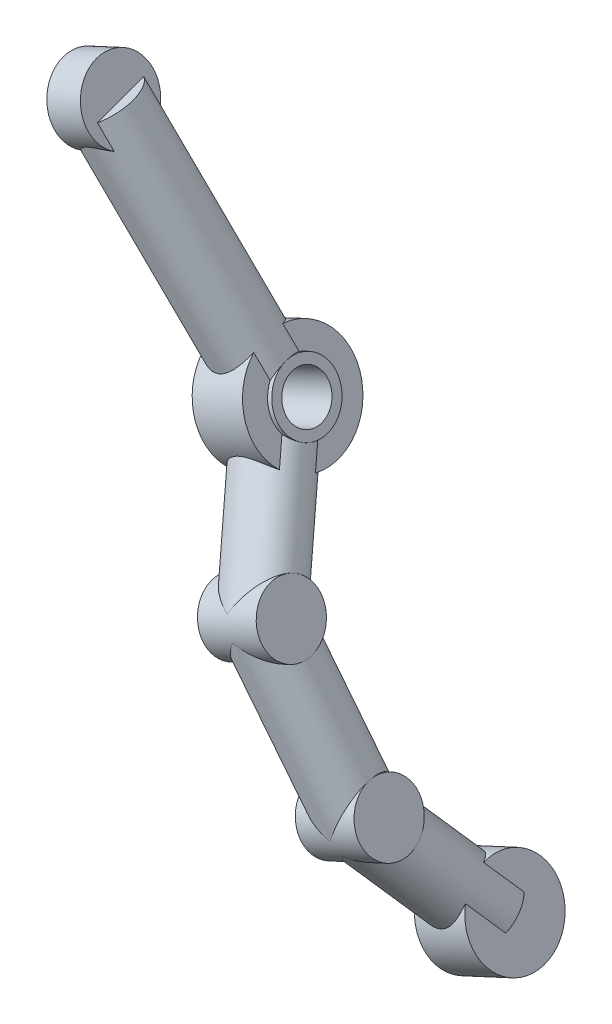
SolidWorks part; units mm, degrees
ref_plane "Alzado" through (0, 0, 0) normal (0, 0, 1) x (1, 0, 0)
ref_plane "Planta" through (0, 0, 0) normal (0, 1, 0) x (1, 0, 0)
ref_plane "Vista lateral" through (0, 0, 0) normal (1, 0, 0) x (0, 0, -1)
sketch3d "Sk_Brazo_1"
  line L0 (424.6109, 411.5791, 33) -> (436.398, 386.181, 26)
  dimension "D1" = 28.8617
sweep "Brazo_1" add path "Sk_Brazo_1" circular profile diameter 7 parameters "D3"=7
sketch3d "Sk_Brazo_2"
  line L0 (436.398, 386.181, 26) -> (442.7125, 372.5749, 34)
  dimension "D1" = 17
sweep "Brazo_2" add path "Sk_Brazo_2" circular profile diameter 7 parameters "D3"=7
sketch3d "Sk_Brazo_3"
  line L0 (442.7125, 372.5749, 34) -> (450.2899, 356.2475, 31)
  dimension "D1" = 18.2483
sweep "Brazo_3" add path "Sk_Brazo_3" circular profile diameter 7 parameters "D3"=7
sketch3d "Sk_Brazo_4"
  line L0 (450.2899, 356.2475, 31) -> (455.3416, 345.3626, 22)
  dimension "D1" = 15
sweep "Brazo_4" add path "Sk_Brazo_4" circular profile diameter 7 parameters "D3"=7
sketch3d "Sk_Brazo_codo_1"
  line L0 (433.2232, 384.7076, 26) -> (439.5728, 387.6544, 26)
  dimension "D1" = 7
sweep "Brazo_codo_1" add path "Sk_Brazo_codo_1" circular profile diameter 7 parameters "D3"=7
sketch3d "Sk_Brazo_codo_2"
  line L0 (439.5378, 371.1015, 34) -> (445.8873, 374.0483, 34)
  dimension "D1" = 7
sweep "Brazo_codo_2" add path "Sk_Brazo_codo_2" circular profile diameter 7 parameters "D3"=7
sketch3d "Sk_Brazo_codo_3"
  line L0 (447.1152, 354.7741, 31) -> (453.4647, 357.7209, 31)
  dimension "D1" = 7
sweep "Brazo_codo_3" add path "Sk_Brazo_codo_3" circular profile diameter 7 parameters "D3"=7
sketch3d "Sk_Ojo_pivote"
  line L0 (433.6768, 384.9181, 26) -> (439.1192, 387.4439, 26)
  dimension "D1" = 6
sweep "Ojo_pivote" add path "Sk_Ojo_pivote" circular profile diameter 12 parameters "D3"=12
sketch3d "Sk_Anclaje_cable"
  line L0 (422.7967, 410.7372, 33) -> (426.425, 412.4211, 33)
  dimension "D1" = 4
sweep "Anclaje_cable" add path "Sk_Anclaje_cable" circular profile diameter 8 parameters "D3"=8
sketch3d "Sk_Ojo_zapata"
  line L0 (452.6203, 344.0997, 22) -> (458.0628, 346.6255, 22)
  dimension "D1" = 6
sweep "Ojo_zapata" add path "Sk_Ojo_zapata" circular profile diameter 10 parameters "D3"=10
sketch3d "Sk_Taladro_pivote"
  line L0 (432.7697, 384.4971, 26) -> (440.0263, 387.8649, 26)
  dimension "D1" = 8
sweep "Taladro_pivote" cut path "Sk_Taladro_pivote" circular profile diameter 5 parameters "D3"=5
